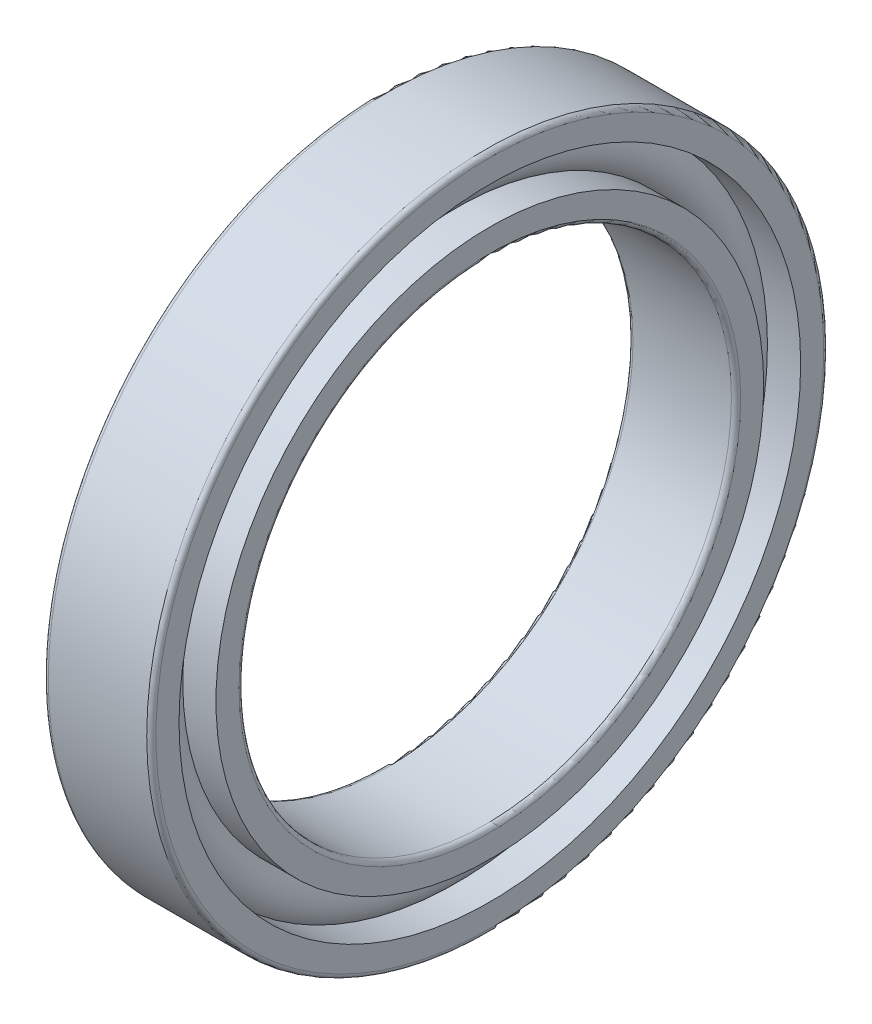
SolidWorks part; units mm, degrees
ref_plane "Plane1" through (0, 0, 0) normal (0, 0, 1) x (1, 0, 0)
ref_plane "Plane2" through (0, 0, 0) normal (0, 1, 0) x (1, 0, 0)
ref_plane "Plane3" through (0, 0, 0) normal (1, 0, 0) x (0, 0, -1)
other "Configuration Table"
sketch "Clipboard" plane through (0, 0, 0) normal (0, 0, 1) x (1, 0, 0)
  line L0 (-10, 0) -> (10, 0) construction
  line L1 (0, 0) -> (22.3471, -0.7804)
  line L2 (0, 0) -> (18.9884, 0.6631)
  line L3 (0, 0) -> (22.3471, -0.7804)
  line L4 (0, 0) -> (-22.3573, -0.3902)
  dimension "BallCLRad" = 19
sketch "CagSpiSke" plane through (0, 0, 0) normal (0, 0, 1) x (1, 0, 0)
  line L0 (0.18, 18.7) -> (0.18, 19.3)
  line L1 (0.18, 19.3) -> (-0.18, 19.3)
  line L2 (-0.18, 19.3) -> (-0.18, 18.7)
  line L3 (-0.18, 18.7) -> (0.18, 18.7)
  line L4 (-20.6375, 0) -> (20.6375, 0) construction
  line L5 (0, 0) -> (0, 23.7692) construction
  dimension "OD" = 38.6
  dimension "ID" = 37.4
revolve "CageSpine" add sketch "CagSpiSke" angle 0.001 about L4 reverse direction yes
ref_axis "Axis1" through (-50, 0, 0) along (1, 0, 0)
sketch "CagBalSke" plane through (0, 0, 0) normal (0, 0, 1) x (1, 0, 0)
  line L0 (-1.98, 19) -> (1.98, 19)
  line L1 (-1.905, 19) -> (1.905, 19) construction
  line L2 (-10, 0) -> (10, 0) construction
  line L3 (0, 0) -> (0, 24) construction
  arc A0 (1.98, 19) -> (-1.98, 19) centre (0, 19) cw
  dimension "BallCLRad" = 19
revolve "CageBall" [suppressed] add sketch "CagBalSke" angle 360 about L1 reverse direction yes
pattern_circular "CageBalls" [suppressed] count 2 every 180 about axis through (-50, 0, 0) along (1, 0, 0)
sketch "CagTrmODSke" plane through (0, 0, 0) normal (0, 0, 1) x (1, 0, 0)
  line L0 (1.981, 19.3) -> (1.981, 20.981)
  line L1 (1.981, 20.981) -> (-1.981, 20.981)
  line L2 (-1.981, 20.981) -> (-1.981, 19.3)
  line L3 (-1.981, 19.3) -> (1.981, 19.3)
  line L4 (-20.6375, 0) -> (20.6375, 0) construction
  line L5 (0, 0) -> (0, 25) construction
  dimension "Width" = 3.962
  dimension "ID" = 38.6
  dimension "OD" = 41.962
revolve "CageTrimOD" [suppressed] cut sketch "CagTrmODSke" angle 360 about L4 reverse direction yes
sketch "CagTrmIDSke" plane through (0, 0, 0) normal (0, 0, 1) x (1, 0, 0)
  line L0 (1.981, 17.021) -> (1.981, 18.7)
  line L1 (1.981, 18.7) -> (-1.981, 18.7)
  line L2 (-1.981, 18.7) -> (-1.981, 17.021)
  line L3 (-1.981, 17.021) -> (1.981, 17.021)
  line L4 (-20.6375, 0) -> (20.6375, 0) construction
  line L5 (0, 0) -> (0, 25) construction
  dimension "Width" = 3.962
  dimension "ID" = 34.042
  dimension "OD" = 37.4
revolve "CageTrimID" [suppressed] cut sketch "CagTrmIDSke" angle 360 about L4 reverse direction yes
sketch "BalSimSke" plane through (0, 0, 0) normal (0, 0, 1) x (1, 0, 0)
  line L0 (-10, 0) -> (10, 0) construction
  line L1 (-10, 19) -> (10, 19) construction
  line L2 (0, 0) -> (0, 23) construction
  circle A0 centre (0, 19) radius 1.8
  dimension "BallCLRad" = 19
  dimension "Ball_diameter" = 3.6
revolve "BallsSimplified" add sketch "BalSimSke" angle 360 about L0
sketch "BalDetSke" plane through (0, 0, 0) normal (0, 0, 1) x (1, 0, 0)
  line L0 (-1.8, 19) -> (1.8, 19)
  line L1 (-1.905, 19) -> (1.905, 19) construction
  line L2 (0, 0) -> (0, 25) construction
  arc A0 (1.8, 19) -> (-1.8, 19) centre (0, 19) cw
  dimension "BallCLRad" = 19
  dimension "Ball_diameter" = 3.6
revolve "BallDetailed" [suppressed] add sketch "BalDetSke" angle 360 about L1 reverse direction yes
sketch "InnRacSke" plane through (0, 0, 0) normal (0, 0, 1) x (1, 0, 0)
  line L0 (-1.3079, 17.8) -> (-3.5, 17.8)
  line L1 (-3.5, 17.8) -> (-3.5, 16.3)
  line L2 (-3.2, 16) -> (3.2, 16)
  line L3 (3.5, 16.3) -> (3.5, 17.8)
  line L4 (3.5, 17.8) -> (1.3079, 17.8)
  line L5 (-20.6375, 0) -> (20.6375, 0) construction
  line L6 (0, 0) -> (0, 30) construction
  arc A0 (-3.5, 16.3) -> (-3.2, 16) centre (-3.2, 16.3) ccw
  arc A1 (3.2, 16) -> (3.5, 16.3) centre (3.2, 16.3) ccw
  arc A2 (1.3079, 17.8) -> (-1.3079, 17.8) centre (0, 19) cw
  dimension "BallCLRad" = 19
  dimension "Fillet_radius" = 0.3
  dimension "Ball_diameter" = 3.55
  dimension "ID" = 32
  dimension "OD" = 35.6
  dimension "Width" = 7
revolve "InnerRace" add sketch "InnRacSke" angle 360 about L5 reverse direction yes
sketch "OutRacSke" plane through (0, 0, 0) normal (0, 0, 1) x (1, 0, 0)
  line L0 (-1.3079, 20.2) -> (-3.5, 20.2)
  line L1 (-3.5, 20.2) -> (-3.5, 21.7)
  line L2 (-3.2, 22) -> (3.2, 22)
  line L3 (3.5, 21.7) -> (3.5, 20.2)
  line L4 (3.5, 20.2) -> (1.3079, 20.2)
  line L5 (-20.6375, 0) -> (20.6375, 0) construction
  line L6 (0, 0) -> (0, 30) construction
  arc A0 (-3.5, 21.7) -> (-3.2, 22) centre (-3.2, 21.7) cw
  arc A1 (3.2, 22) -> (3.5, 21.7) centre (3.2, 21.7) cw
  arc A2 (1.3079, 20.2) -> (-1.3079, 20.2) centre (0, 19) ccw
  dimension "BallCLRad" = 19
  dimension "Fillet_radius" = 0.3
  dimension "Ball_diameter" = 3.55
  dimension "Width" = 7
revolve "OuterRace" add sketch "OutRacSke" angle 360 about L5 reverse direction yes
pattern_circular "BallsDetailed" [suppressed] count 2 every 180 about axis through (-50, 0, 0) along (1, 0, 0)
equation "\"BallCLRad@Clipboard\" = ( \"OD@OutRacSke\" + \"ID@InnRacSke\" ) / 4"
equation "\"BallCLRad@BalSimSke\" = \"BallCLRad@Clipboard\""
equation "\"BallCLRad@BalDetSke\" = \"BallCLRad@Clipboard\""
equation "\"BallCLRad@InnRacSke\" = \"BallCLRad@Clipboard\""
equation "\"BallCLRad@OutRacSke\" = \"BallCLRad@Clipboard\""
equation "\"Ball_diameter@InnRacSke\" = \"Ball_diameter@BalDetSke\" - 0.05"
equation "\"Ball_diameter@OutRacSke\" = \"Ball_diameter@BalDetSke\" - 0.05"
equation "\"Ball_diameter@BalSimSke\" = \"Ball_diameter@BalDetSke\""
equation "\"Width@OutRacSke\" = \"Width@InnRacSke\""
equation "\"Fillet_radius@OutRacSke\" = \"Fillet_radius@InnRacSke\""
equation "\"Max_count@Clipboard\" = int( 3.14159265 / atn(( \"Ball_diameter@BalDetSke\" / 2) / sqr( \"BallCLRad@Clipboard\"  *  \"BallCLRad@Clipboard\" - ( \"Ball_diameter@BalDetSke\" / 2) *  ( \"Ball_diameter@BalDetSke\" / 2))))"
equation "\"Max_count@Clipboard\" = ((sgn( \"Max_count@Clipboard\" - \"Count@Clipboard\" )-1)*( \"Max_count@Clipboard\" - \"Count@Clipboard\" ))/-2+ \"Count@Clipboard\""
equation "\"Count@BallsDetailed\" = int( \"Show_count@Clipboard\" ) "
equation "\"Count@BallsDetailed\" = ((sgn( \"Count@BallsDetailed\" - \"Max_count@Clipboard\" )-1)*( \"Count@BallsDetailed\" - \"Max_count@Clipboard\" ))/-2+ \"Max_count@Clipboard\""
equation "\"Count@BallsDetailed\" = ((sgn( \"Count@BallsDetailed\" - \"Min_count@Clipboard\" )+1)*( \"Count@BallsDetailed\" - \"Min_count@Clipboard\"))/2 +\"Min_count@Clipboard\""
equation "\"Angle@BallsDetailed\" = 360.0 / \"Max_count@Clipboard\""
equation "\"BallCLRad@CagBalSke\" = \"BallCLRad@Clipboard\""
equation "\"Count@CageBalls\" = \"Count@BallsDetailed\""
equation "\"Angle@CageBalls\" = \"Angle@BallsDetailed\""
equation "\"Angle@CageSpine\" =  \"Angle@CageBalls\" * ( \"Count@CageBalls\" -1 + int( \"Count@CageBalls\" / \"Max_count@Clipboard\" ) )  + 0.001 -  int( \"Count@CageBalls\" / \"Max_count@Clipboard\" ) * 0.001"
equation "\"Angle@CageSpine\" =  \"Angle@CageSpine\" * int( \"Min_count@Clipboard\" / 2) + int(1 / \"Min_count@Clipboard\")  * 0.001"
equation "\"CageWallOD@CagBalSke\" =  \"Ball_diameter@BalDetSke\" * 1.1"
equation "\"Thickness@CagSpiSke\" =  \"Ball_diameter@BalDetSke\" * 0.1"
equation "\"OD@CagTrmODSke\" = \"BallCLRad@Clipboard\" * 2 + \"CageWallOD@CagBalSke\" + 0.002"
equation "\"ID@CagTrmODSke\" = \"BallCLRad@Clipboard\" * 2 + \"Ball_diameter@BalDetSke\" / 6"
equation "\"OD@CagTrmIDSke\" = \"BallCLRad@Clipboard\" * 2 - \"Ball_diameter@BalDetSke\" / 6"
equation "\"ID@CagTrmIDSke\" = \"BallCLRad@Clipboard\" * 2 - \"CageWallOD@CagBalSke\" + 0.002"
equation "\"OD@CagSpiSke\" = \"ID@CagTrmODSke\""
equation "\"ID@CagSpiSke\" = \"OD@CagTrmIDSke\""
equation "\"Width@CagTrmODSke\" = \"CageWallOD@CagBalSke\" + 0.002"
equation "\"Width@CagTrmIDSke\" = \"CageWallOD@CagBalSke\" + 0.002"
